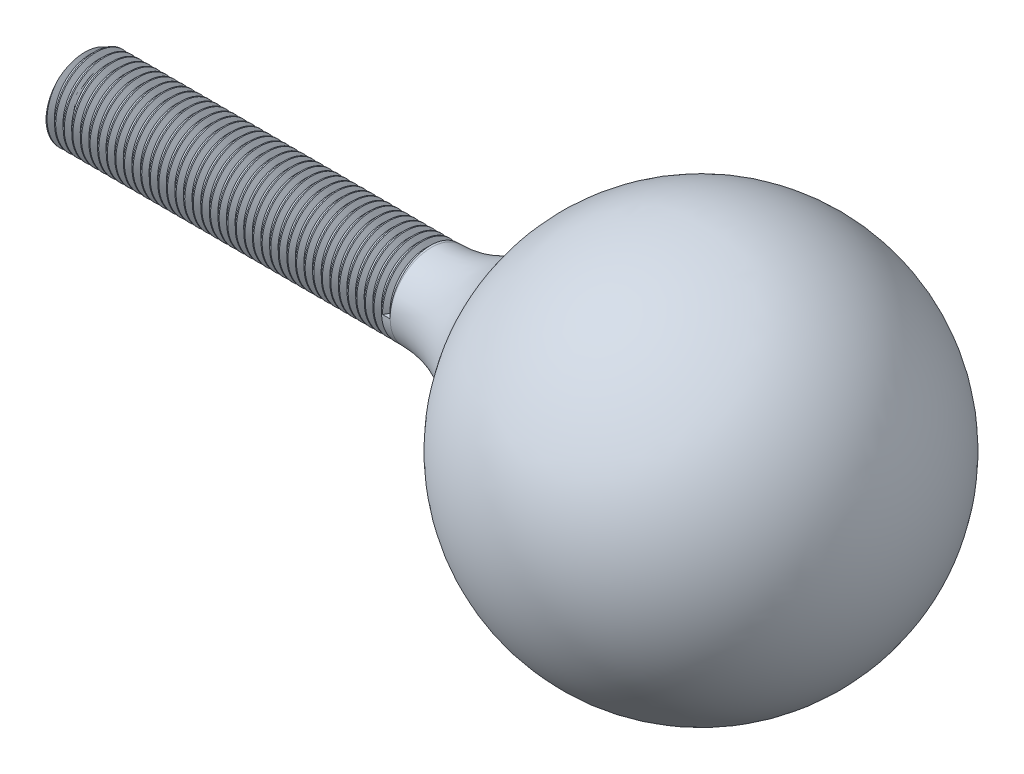
SolidWorks part; units mm, degrees
material "Glass"
ref_plane "Front Plane" through (0, 0, 0) normal (0, 0, 1) x (1, 0, 0)
ref_plane "Top Plane" through (0, 0, 0) normal (0, 1, 0) x (1, 0, 0)
ref_plane "Right Plane" through (0, 0, 0) normal (1, 0, 0) x (0, 0, -1)
sketch "Sketch1" plane through (0, 0, 0) normal (0, 0, 1) x (1, 0, 0)
  line L0 (0, 0) -> (0, 31355.6932) construction
  line L1 (0, 0) -> (31355.6932, 0) construction
  line L2 (0, 0) -> (50, 0)
  line L3 (0, 0) -> (0, 6)
  line L5 (0, 6) -> (50, 6)
  line L6 (117.6212, 0) -> (50, 0)
  arc A0 (50, 6) -> (64.583, 14.3666) centre (50, 22.8924) ccw
  arc A1 (64.583, 14.3666) -> (117.6212, 0) centre (89.1563, 0) cw
  dimension "D3" = 16.8924
  dimension "D4" = 28.4649
  dimension "D1" = 50
  dimension "D2" = 12
  dimension "D5" = 117.6212
revolve "Revolve2" add sketch "Sketch1" angle 360 about L1
thread "Thread1" pitch 1.25 profile "Thread Profile1" start angle 0, offset 0, length 70, pitch 1.25, diameter 12
ref_plane "Plane1" through (50, 0, 6) normal (0, -1, 0) x (0, 0, 1)
sketch "Thread Profile1" plane through (50, 0, 6) normal (0, -1, 0) x (0, 0, 1)
  line L0 (0, 0) -> (0, 1.25) construction
  line L11 (0, 0) -> (0, 1.0937)
  line L12 (0, 1.0937) -> (-0.6766, 0.7031)
  line L13 (-0.6766, 0.7031) -> (-0.6766, 0.3906)
  line L15 (-0.6766, 0.3906) -> (0, 0)
  line L17 (-0.6766, 0.5469) -> (0, 0.5469) construction
  point P2 (0, 0)
  dimension "Pitch" = 1.25
  dimension "Profile_Angle" = 60
  dimension "Profile_Land" = 0.3125
  dimension "Profile_Height" = 0.6766
